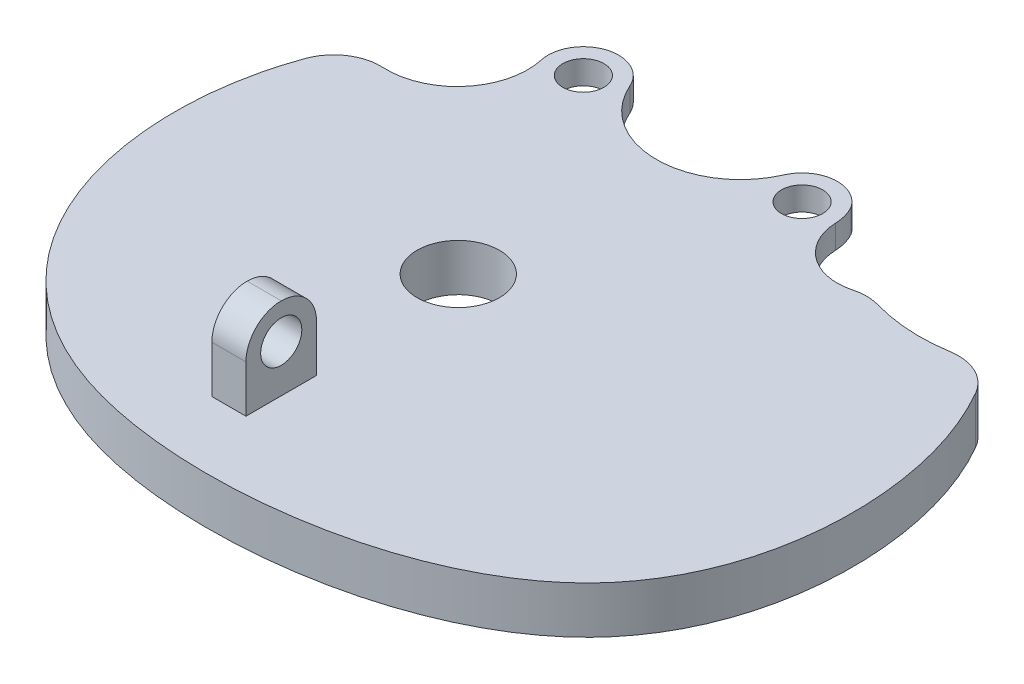
SolidWorks part; units mm, degrees
other "Markup1"
sketch "Sketch52"
ref_plane "Front Plane" through (0, 0, 0) normal (0, 0, 1) x (1, 0, 0)
ref_plane "Top Plane" through (0, 0, 0) normal (0, 1, 0) x (1, 0, 0)
ref_plane "Right Plane" through (0, 0, 0) normal (1, 0, 0) x (0, 0, -1)
sketch "Sketch1" plane through (0, 0, 0) normal (0, -1, 0) x (1, 0, 0)
  spline S0 degree 3 poles (-30.0009, -3.8631) (-6.7916, -35.506) (37.8139, -21.5057) (32.9254, 23.6369) (-15.2616, 29.425) (-30.0009, -3.8631) (-6.7916, -35.506) (37.8139, -21.5057) knots -0.582232 -0.423204 -0.235785 0 0.296836 0.417768 0.576796 0.764215 1 1.296836 1.417768 1.576796 only from (-5, -26) to (-5, -26)
  dimension "D1" = 24
  dimension "D3" = 5
  dimension "D5" = 26
extrude "Boss-Extrude1" add sketch "Sketch1" against normal blind 4
sketch "Sketch53" plane through (0, 0, 0) normal (0, -1, 0) x (1, 0, 0)
  circle A0 centre (0, 0) radius 3.5
  dimension "D1" = 7
extrude "Cut-Extrude1" cut sketch "Sketch53" against normal through all
sketch "Sketch54" plane through (0, 4, 0) normal (0, 1, 0) x (1, 0, 0)
  line L0 (0, 33.4854) -> (0, -33.4854) construction
  line L1 (0, 0) -> (21130.9131, 45315.3894) construction
  circle A0 centre (9.2976, 19.9388) radius 1.75
  circle A2 centre (-9.2976, 19.9388) radius 1.75
  point P7 (0, 0)
  dimension "D3" = 3.5
  dimension "D1" = 22
  dimension "D2" = 25
extrude "Cut-Extrude2" cut sketch "Sketch54" against normal up to next
sketch "Sketch55" plane through (0, 0, 0) normal (0, -1, 0) x (1, 0, 0)
  line L0 (0, 0) -> (0, -50000) construction
  line L1 (0, 0) -> (-21130.9131, -45315.3894) construction
  circle A0 centre (-10.5655, -22.6577) radius 6.5
  circle A1 centre (10.5655, -22.6577) radius 6.5
  dimension "D3" = 13
  dimension "D1" = 25
  dimension "D2" = 25
extrude "Cut-Extrude3" cut sketch "Sketch55" against normal blind 2
sketch "Sketch57" plane through (0, 4, 0) normal (0, 1, 0) x (1, 0, 0)
  line L0 (-22.0606, 22.495) -> (0, 42)
  line L1 (0, 42) -> (22.3044, 44.8768)
  arc A0 (-6.5484, 21.1396) -> (6.5484, 21.1396) centre (0, 24) ccw
  arc A1 (11.7852, 21.6156) -> (6.5484, 21.1396) centre (9.2976, 19.9388) ccw
  arc A2 (-6.5484, 21.1396) -> (-12.2272, 19.2925) centre (-9.2976, 19.9388) ccw
  arc A3 (-22.0606, 22.495) -> (-12.2272, 19.2925) centre (-18.0863, 18) ccw
  arc A4 (11.7852, 21.6156) -> (12.3798, 20.7948) centre (24.2231, 30) ccw
  arc A5 (12.3798, 20.7948) -> (18.9178, 15.9696) centre (16.7976, 19.9388) ccw
  arc A6 (18.9178, 15.9696) -> (22.3044, 44.8768) centre (24.2231, 30) ccw
  circle A7 centre (-9.2976, 19.9388) radius 1.75 construction
  dimension "D2" = 18
  dimension "D3" = 6
  dimension "D5" = 12
  dimension "D6" = 30
  dimension "D8" = 9
  dimension "D1" = 24
  dimension "D4" = 30
  dimension "D7" = 42
extrude "Cut-Extrude4" cut sketch "Sketch57" against normal up to next
fillet "Fillet1" radius 4 8 edges at (18.9178, 2, -15.9696) (12.3798, 3, -20.7948) (-12.305, 1, -16.3948) (-5.1566, 1, -19.053) (5.1566, 1, -19.053) (13.512, 1, -16.8639)
sketch "Sketch58" plane through (0, 4, 0) normal (0, 1, 0) x (1, 0, 0)
  line L1 (-1.45, -13.5) -> (1.45, -13.5)
  line L2 (-1.45, -13.5) -> (-1.45, -19.5)
  line L3 (-1.45, -19.5) -> (1.45, -19.5)
  line L4 (1.45, -13.5) -> (1.45, -19.5)
  line L5 (-1.45, -13.5) -> (1.45, -19.5) construction
  line L6 (-1.45, -19.5) -> (1.45, -13.5) construction
  point P0 (0, -16.5)
  dimension "D1" = 6
  dimension "D2" = 16.5
  dimension "D3" = 2.9
extrude "Boss-Extrude3" add sketch "Sketch58" along normal blind 7
sketch "Sketch59" plane through (1.45, 0, 0) normal (1, 0, 0) x (0, 0, -1)
  line L0 (-19.5, 4) -> (-13.5, 4) construction
  circle A0 centre (-16.5, 8) radius 1.75
  point P5 (-16.5, 4)
  dimension "D2" = 3.5
  dimension "D1" = 4
extrude "Cut-Extrude5" cut sketch "Sketch59" against normal up to next
fillet "Fillet2" radius 3 2 edges at (0, 11, 13.5) (0, 11, 19.5)
